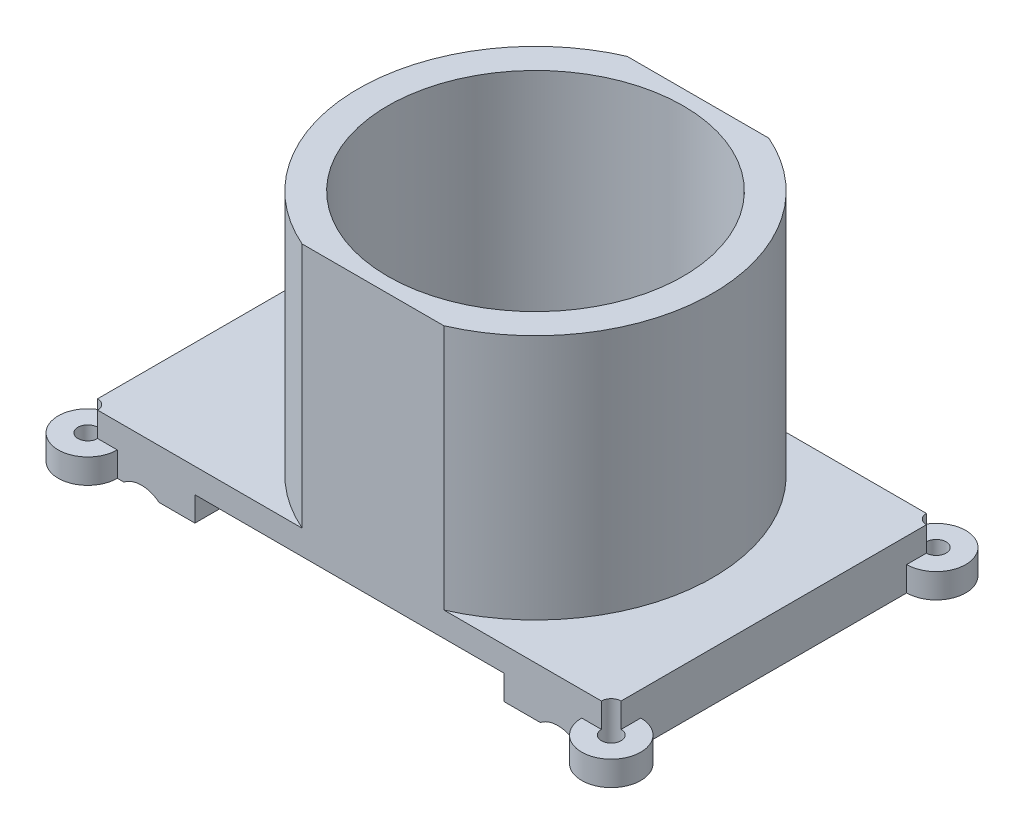
SolidWorks part; units mm, degrees
ref_plane "前视" through (0, 0, 0) normal (0, 0, 1) x (1, 0, 0)
ref_plane "上视" through (0, 0, 0) normal (0, 1, 0) x (1, 0, 0)
ref_plane "右视" through (0, 0, 0) normal (1, 0, 0) x (0, 0, -1)
sketch "Sketch1" plane through (0, 0, 0) normal (0, 1, 0) x (1, 0, 0)
  line L0 (53.16, -33) -> (-53.16, -33)
  line L1 (53.16, -33) -> (53.16, 33)
  line L2 (-53.16, -33) -> (-53.16, 33)
  line L3 (53.16, 33) -> (-53.16, 33)
  line L4 (53.16, -33) -> (-53.16, 33) construction
  line L5 (-53.16, -33) -> (53.16, 33) construction
  line L6 (-31.4, 33) -> (-31.4, -33)
  line L7 (31.4, 33) -> (31.4, -33)
  point P1 (0, 0)
  dimension "D1" = 106.32
  dimension "D2" = 66
  dimension "D3" = 21.76
  dimension "D4" = 21.76
extrude "Boss-Extrude1" add sketch "Sketch1" along normal blind 10 contours L6 L3 L2 L0 | L7 L3 L6 L0 | L3 L7 L0 L1 region at (42.28, 0, 0) region at (0, 0, 0) region at (-42.28, 0, 0)
extrude "Cut-Extrude1" cut sketch "Sketch1<5>" along normal blind 5 contours L7 L3 L6 L0 region at (0, 0, 0)
sketch "Sketch1<5>" plane through (0, 0, 0) normal (0, 1, 0) x (1, 0, 0) same geometry as "Sketch1"
ref_plane "Plane1" through (0, 0, 31) normal (0, 0, 1) x (1, 0, 0)
sketch "Sketch3" plane through (0, 0, 31) normal (0, 0, 1) x (1, 0, 0)
  line L0 (-53.16, 10) -> (-53.16, 0) construction
  line L1 (-31.4, 0) -> (-53.16, 0) construction
  line L2 (53.16, 10) -> (53.16, 0) construction
  line L3 (53.16, 0) -> (31.4, 0) construction
  circle A0 centre (-42.25, -4.5) radius 7.65
  circle A1 centre (42.31, -4.5) radius 7.65
  circle A2 centre (42.31, -4.5) radius 5.75
  circle A3 centre (-42.25, -4.5) radius 5.75
  point P0 (-42.25, -4.5)
  point P7 (42.31, -4.5)
  dimension "D3" = 10.85
  dimension "D1" = 10.91
  dimension "D2" = 4.5
  dimension "D4" = 4.5
extrude "Cut-Extrude2" cut sketch "Sketch3" against normal offset from surface (62 mm away) 2 contours A3 | A0 A3 | A2 | A1 A2 region at (-49.6836, -4.5, 31) region at (34.8764, -4.5, 31) region at (42.31, -4.5, 31) region at (-42.25, -4.5, 31) up to face at (0, 3.75, -33)
extrude "Cut-Extrude3" cut sketch "Sketch3<3>" against normal through all both and the other way through all contours A2 | A3 region at (42.31, -4.5, 31) region at (-42.25, -4.5, 31)
sketch "Sketch3<3>" plane through (0, 0, 31) normal (0, 0, 1) x (1, 0, 0) same geometry as "Sketch3"
sketch "Sketch4" plane through (0, 0, 0) normal (0, -1, 0) x (1, 0, 0)
  line L0 (-47.16, 33) -> (-53.16, 33)
  line L1 (-53.16, 33) -> (-53.16, 27)
  line L2 (-47.16, -33) -> (-53.16, -33)
  line L3 (-53.16, -33) -> (-53.16, -27)
  line L4 (53.16, -27) -> (53.16, -33)
  line L5 (53.16, -33) -> (47.16, -33)
  line L6 (47.16, 33) -> (53.16, 33)
  line L7 (53.16, 33) -> (53.16, 27)
  circle A0 centre (53.16, 33) radius 6
  circle A1 centre (53.16, -33) radius 6
  circle A2 centre (-53.16, -33) radius 6
  circle A3 centre (-53.16, 33) radius 6
  circle A4 centre (53.16, 33) radius 2
  circle A5 centre (53.16, -33) radius 2
  circle A6 centre (-53.16, -33) radius 2
  circle A7 centre (-53.16, 33) radius 2
  line M1 (53.16, 33) -> (45.8895, 33)
  line M7 (45.8895, -33) -> (53.16, -33)
  line M8 (53.16, -33) -> (53.16, 33)
extrude "Boss-Extrude2" add sketch "Sketch4" against normal blind 5 contours A4 A0 L6 M8 | A5 A1 L4 M7 | A7 L0 A3 L1 | A6 L3 A2 L2 region at (-49.16, 0, 33.1697) region at (-57.2826, 0, -37.1226) region at (57.2826, 0, -28.8774) region at (53.3297, 0, 29)
extrude "Cut-Extrude4" cut sketch "Sketch4<3>" against normal through all contours A4 L7 M1 | A5 L5 M8 | L2 A6 L3 | L1 A7 L0 region at (-52.3112, 0, 32.1512) region at (-52.3112, 0, -32.1512) region at (52.3112, 0, -32.1512) region at (52.3112, 0, 32.1512)
sketch "Sketch4<3>" plane through (0, 0, 0) normal (0, -1, 0) x (1, 0, 0) same geometry as "Sketch4"
sketch "Sketch5" plane through (0, 10, 0) normal (0, 1, 0) x (1, 0, 0)
  line L2 (53.16, -27) -> (53.16, 27) construction
  line L3 (31.4, 33) -> (-31.4, 33) construction
  line L4 (19.1575, -33) -> (-9.6175, -33)
  line L5 (51.16, -33) -> (-51.16, -33) construction
  line L6 (-9.6175, 33) -> (19.1575, 33)
  line L7 (51.16, 33) -> (-51.16, 33) construction
  circle A0 centre (4.77, 0) radius 30
  circle A1 centre (4.77, 0) radius 36
  point P0 (4.77, 0)
  line M2 (-51.16, -33) -> (51.16, -33)
  line M6 (51.16, 33) -> (-51.16, 33)
  dimension "D1" = 48.39
  dimension "D2" = 33
extrude "Cut-Extrude5" cut sketch "Sketch5" against normal through all contours A0 region at (4.77, 10, 0)
extrude "Boss-Extrude3" add sketch "Sketch5<3>" along normal blind 50 contours A1 A0 M2 M6 region at (4.77, 10, 32.0233)
sketch "Sketch5<3>" plane through (0, 10, 0) normal (0, 1, 0) x (1, 0, 0) same geometry as "Sketch5"
